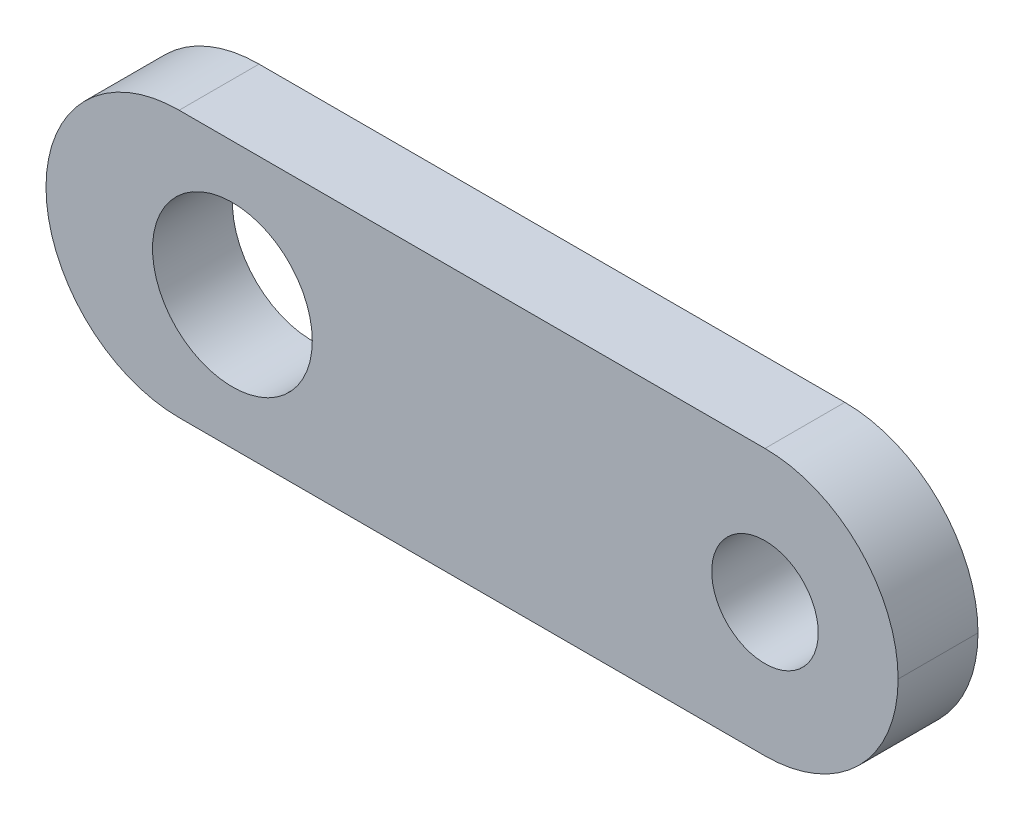
SolidWorks part; units mm, degrees
ref_plane "前视基准面" through (0, 0, 0) normal (0, 0, 1) x (1, 0, 0)
ref_plane "上视基准面" through (0, 0, 0) normal (0, 1, 0) x (1, 0, 0)
ref_plane "右视基准面" through (0, 0, 0) normal (1, 0, 0) x (0, 0, -1)
other "Configuration Table"
sketch "草图1" plane through (0, 0, 0) normal (0, 0, 1) x (1, 0, 0)
  line L0 (25, 0) -> (-7, 0) construction
  line L1 (-25, 0) -> (25, 0) construction
  line L3 (3, 0) -> (20, 0) construction
  line L4 (-7, -5) -> (25, -5)
  line L5 (-7, -5) -> (-7, 5)
  line L6 (-7, 5) -> (25, 5)
  line L7 (25, -5) -> (25, 5)
  line L8 (-7, -5) -> (25, 5) construction
  line L9 (-7, 5) -> (25, -5) construction
  circle A0 centre (0, 0) radius 25 construction
  circle A1 centre (0, 0) radius 3
  circle A3 centre (20, 0) radius 2
  point P4 (9, 0)
  point P6 (0, 0)
  point P9 (0, 0)
  dimension "D1" = 10
extrude "凸台-拉伸1" add sketch "草图1" along normal blind 3
fillet "圆角1" radius 5 4 edges at (25, -5, 1.5) (25, 5, 1.5) (-7, -5, 1.5) (-7, 5, 1.5)
